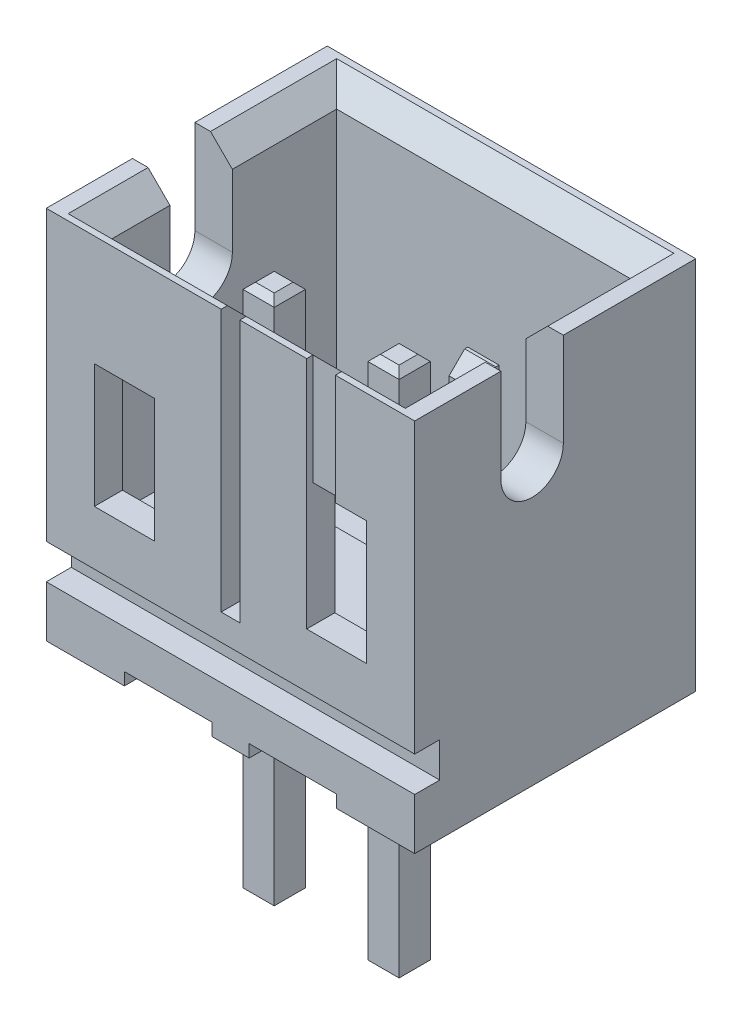
SolidWorks part; units mm, degrees
ref_plane "Спереди" through (0, 0, 0) normal (0, 0, 1) x (1, 0, 0)
ref_plane "Сверху" through (0, 0, 0) normal (0, 1, 0) x (1, 0, 0)
ref_plane "Справа" through (0, 0, 0) normal (1, 0, 0) x (0, 0, -1)
sketch "Body1" plane through (0, 0, 0) normal (0, 1, 0) x (1, 0, 0)
  line L1 (5.9, -4.5) -> (0, -4.5)
  line L2 (5.9, -4.5) -> (5.9, 0)
  line L3 (5.9, 0) -> (0, 0)
  line L4 (0, -4.5) -> (0, 0)
  dimension "depth" = 4.5
  dimension "width" = 5.9
extrude "Бобышка-Вытянуть1" add sketch "Body1" along normal blind 6
sketch "Эскиз2" plane through (0, 6, 0) normal (0, 1, 0) x (1, 0, 0)
  line L0 (5.3, -4.05) -> (5.3, -0.45)
  line L1 (5.3, -0.45) -> (0.6, -0.45)
  line L2 (0.6, -0.45) -> (0.6, -4.05)
  line L3 (0.6, -4.05) -> (5.3, -4.05)
  line L4 (0.6, -0.45) -> (5.3, -4.05) construction
  line L5 (2.95, 0) -> (2.95, -4.5) construction
  line L6 (5.9, 0) -> (0, 0) construction
  line L7 (0, -4.5) -> (5.9, -4.5) construction
  line L12 (0, 0) -> (0, -4.5) construction
  point P16 (2.95, -2.25)
  dimension "D1" = 3.6
  dimension "D2" = 0.6
extrude "Вырез-Вытянуть1" cut sketch "Эскиз2" against normal offset from surface (4.2 mm away) 1.8 up to face at (2.95, 0, 2.25)
sketch "Эскиз3" plane through (0, 0, 4.5) normal (0, 0, 1) x (1, 0, 0)
  line L0 (2.95, 6) -> (2.95, 0) construction
  line L1 (0, 6) -> (5.9, 6) construction
  line L2 (0, 0) -> (5.9, 0) construction
  line L8 (0, 6) -> (0, 0) construction
  line L9 (5.9, 1.38) -> (0, 1.38)
  line L11 (5.9, 0.82) -> (0, 0.82)
  line L12 (0, 1.38) -> (0, 0.82)
  line L13 (5.9, 1.38) -> (5.9, 0.82)
  point P13 (2.95, 0.82)
  point P14 (2.95, 1.38)
  dimension "D1" = 0.82
  dimension "D2" = 0.56
extrude "Вырез-Вытянуть2" cut sketch "Эскиз3" against normal blind 0.4
chamfer "Фаска1" distance 0.35 angle 45 4 edges at (5.3, 6, 2.25) (2.95, 6, 4.05) (0.6, 6, 2.25) (2.95, 6, 0.45)
sketch "Эскиз4" plane through (0, 0, 4.5) normal (0, 0, 1) x (1, 0, 0)
  line L0 (2.95, 1.38) -> (2.95, 0) construction
  line L4 (0, 0) -> (5.9, 0) construction
  line L5 (0, 6) -> (0, 1.38) construction
  line L6 (0.77, 4.23) -> (1.73, 4.23)
  line L7 (0.77, 4.23) -> (0.77, 2.25)
  line L8 (0.77, 2.25) -> (1.73, 2.25)
  line L9 (1.73, 4.23) -> (1.73, 2.25)
  line L10 (5.13, 2.25) -> (4.17, 2.25)
  line L11 (4.17, 4.23) -> (4.17, 2.25)
  line L12 (5.13, 4.23) -> (4.17, 4.23)
  line L13 (5.13, 4.23) -> (5.13, 2.25)
  line L14 (5.9, 1.38) -> (0, 1.38) construction
  dimension "D1" = 0.96
  dimension "D2" = 1.98
  dimension "D3" = 0.77
  dimension "D4" = 2.25
extrude "Вырез-Вытянуть3" cut sketch "Эскиз4" against normal up to next
sketch "Эскиз5" plane through (0, 0, 4.5) normal (0, 0, 1) x (1, 0, 0)
  line L0 (0, 0) -> (5.9, 0) construction
  line L1 (1.25, 0.2) -> (2.65, 0.2)
  line L2 (1.25, 0.2) -> (1.25, 0)
  line L3 (1.25, 0) -> (2.65, 0)
  line L4 (2.65, 0.2) -> (2.65, 0)
  line L6 (2.95, 0.82) -> (2.95, 0) construction
  line L7 (0, 0.82) -> (5.9, 0.82) construction
  line L12 (1.95, 0.82) -> (1.95, 0) construction
  line L13 (0, 0.82) -> (0, 0) construction
  point P14 (1.95, 0.2)
  dimension "D1" = 1.95
  dimension "D2" = 1.4
  dimension "D3" = 0.2
extrude "Вырез-Вытянуть4" cut sketch "Эскиз5" against normal through all
sketch "Эскиз7" plane through (0, 0, 4.5) normal (0, 0, 1) x (1, 0, 0)
  line L0 (0, 6) -> (5.9, 6) construction
  line L1 (4.17, 6) -> (4.63, 6)
  line L2 (4.17, 6) -> (4.17, 4.23)
  line L3 (4.17, 4.23) -> (4.63, 4.23)
  line L4 (4.63, 6) -> (4.63, 4.23)
  line L5 (5.13, 4.23) -> (4.17, 4.23) construction
  line L6 (4.17, 4.23) -> (4.17, 2.25) construction
  dimension "D1" = 0.5
extrude "Вырез-Вытянуть5" cut sketch "Эскиз7" against normal blind 0.1
sketch "Эскиз8" plane through (0, 0, 4.5) normal (0, 0, 1) x (1, 0, 0)
  line L0 (2.95, 0.82) -> (2.95, 1.38) construction
  line L1 (0, 0.82) -> (5.9, 0.82) construction
  line L2 (5.9, 1.38) -> (0, 1.38) construction
  line L3 (2.95, 2.5686) -> (2.95, 0.2176) construction
  line L4 (0, 6) -> (4.17, 6) construction
  line L5 (3.1, 6) -> (2.8, 6)
  line L6 (3.1, 6) -> (3.1, 1.8)
  line L7 (3.1, 1.8) -> (2.8, 1.8)
  line L9 (0, 6) -> (0, 1.38) construction
  line L10 (2.8, 6) -> (2.8, 1.8)
  line L11 (0, 0) -> (1.25, 0) construction
  point P20 (2.95, 6)
  point P21 (2.95, 1.8)
  dimension "D1" = 3.1
  dimension "D2" = 1.8
extrude "Вырез-Вытянуть6" cut sketch "Эскиз8" against normal up to next
sketch "Эскиз9" plane through (0, 0, 0) normal (-1, 0, 0) x (0, 0, 1)
  line L0 (0, 6) -> (4.5, 6) construction
  line L1 (2.12, 6) -> (3.12, 6)
  line L2 (2.12, 6) -> (2.12, 4.5)
  line L3 (2.12, 4.5) -> (3.12, 4.5) construction
  line L4 (3.12, 6) -> (3.12, 4.5)
  line L5 (4.5, 6) -> (4.5, 1.38) construction
  arc A0 (2.12, 4.5) -> (3.12, 4.5) centre (2.62, 4.5) ccw
  point P10 (2.62, 6)
  dimension "D1" = 1
  dimension "D2" = 1.38
  dimension "D3" = 1.5
extrude "Вырез-Вытянуть7" cut sketch "Эскиз9" against normal up to next
ref_plane "Плоскость1" through (2.95, 0, 0) normal (1, 0, 0) x (0, 0, -1)
mirror "Зеркальное отражение1" about plane through (2.95, 0, 0) normal (1, 0, 0) of "Вырез-Вытянуть7"
sketch "Эскиз15" plane through (0, 1.8, 0) normal (0, 1, 0) x (1, 0, 0)
  line L1 (0.6, -0.45) -> (5.3, -0.45)
  line L2 (0.6, -0.45) -> (0.6, -2.4)
  line L3 (0.6, -2.4) -> (5.3, -2.4)
  line L4 (5.3, -0.45) -> (5.3, -2.4)
  line L8 (5.3, -0.45) -> (0.6, -0.45) construction
  line L9 (5.3, -2.12) -> (5.3, -0.45) construction
  line L10 (0.6, -4.05) -> (0.6, -0.45) construction
  line L11 (2.8, -4.05) -> (0.6, -4.05) construction
  dimension "D1" = 1.65
extrude "Вырез-Вытянуть9" cut sketch "Эскиз15" against normal blind 0.65 contours L3 L4 L1 L2
chamfer "Фаска7" distance 0.65 angle 45 1 edges at (2.95, 1.15, 2.4)
sketch "Эскиз10" plane through (0, 0, 0.45) normal (0, 0, 1) x (1, 0, 0)
  line L1 (2.7, 3.4) -> (3.2, 3.4)
  line L2 (2.7, 3.4) -> (2.7, 1.15)
  line L3 (2.7, 1.15) -> (3.2, 1.15)
  line L4 (3.2, 3.4) -> (3.2, 1.15)
  line L5 (2.95, 3.4) -> (2.95, 1.15) construction
  line L6 (0, 6) -> (0, 0) construction
  line L9 (0.6, 1.15) -> (5.3, 1.15) construction
  dimension "D2" = 2.95
  dimension "D3" = 0.25
  dimension "D4" = 2.25
extrude "Бобышка-Вытянуть2" add sketch "Эскиз10" along normal blind 0.3
chamfer "Фаска2" distance 0.25 angle 45 1 edges at (2.95, 3.4, 0.75)
pattern_linear "Линейный массив3" [suppressed] count 1 spacing 2 of bodies 112
sketch "Эскиз12" plane through (0, 0.2, 0) normal (0, -1, 0) x (1, 0, 0)
  line L0 (1.7, 3.05) -> (2.2, 2.55) construction
  line L1 (1.7, 3.05) -> (2.2, 3.05)
  line L2 (1.7, 3.05) -> (1.7, 2.55)
  line L3 (1.7, 2.55) -> (2.2, 2.55)
  line L4 (2.2, 3.05) -> (2.2, 2.55)
  line L5 (2.65, 4.5) -> (1.25, 4.5) construction
  line L6 (0, 0) -> (0, 4.5) construction
  point P4 (1.95, 2.8)
  dimension "D1" = 0.5
  dimension "D2" = 1.7
  dimension "D3" = 1.95
extrude "Бобышка-Вытянуть4" add sketch "Эскиз12" against normal blind 4.9 and the other way blind 3.6
chamfer "Фаска3" distance 0.1 angle 45 4 edges at (1.95, -3.4, 3.05) (2.2, -3.4, 2.8) (1.95, -3.4, 2.55) (1.7, -3.4, 2.8)
chamfer "Фаска4" distance 0.1 angle 45 4 edges at (1.95, 5.1, 2.55) (2.2, 5.1, 2.8) (1.95, 5.1, 3.05) (1.7, 5.1, 2.8)
pattern_linear "Линейный массив2" count 2 spacing 2 along (1, 0, 0) of "Бобышка-Вытянуть4", "Фаска4", "Фаска3", "Вырез-Вытянуть4"
sketch "Эскиз16" plane through (0, 0, 0) normal (0, -1, 0) x (1, 0, 0)
  line L0 (1.7, 3.05) -> (2.2, 2.55) construction
  circle A0 centre (1.95, 2.8) radius 0.05
  point P4 (1.95, 2.8)
  dimension "D1" = 0.1
extrude "Вырез-Вытянуть10" cut sketch "Эскиз16" along normal up to surface (3.4 mm away) up to face at (1.95, -3.4, 2.8)
equation "\"PINS\" = 2'enter the number of pins you need"
equation "\"width@Body1\"= 3.9 + 2.0 * ( \"PINS\" - 1 )"
equation "\"PIN_MASS\"= \"PINS\""
equation "\"D1@Линейный массив2\"=\"PIN_MASS\""
equation "\"GUIDE_MASS\"= \"PINS\" - 1"
equation "\"D1@Линейный массив3\"=\"GUIDE_MASS\""
